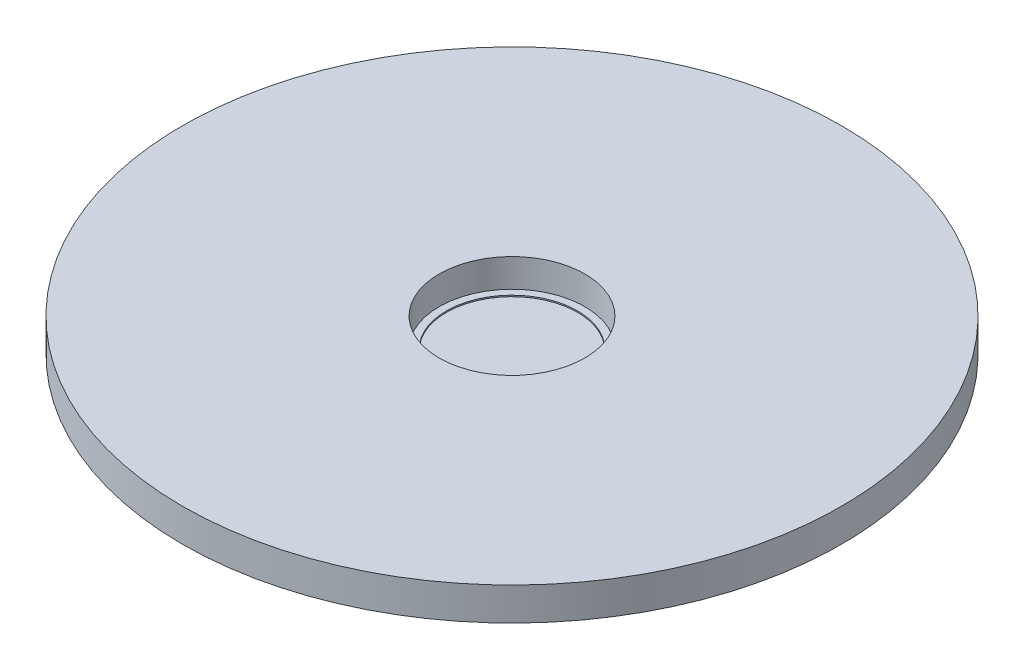
SolidWorks part; units mm, degrees
ref_plane "Front Plane" through (0, 0, 0) normal (0, 0, 1) x (1, 0, 0)
ref_plane "Top Plane" through (0, 0, 0) normal (0, 1, 0) x (1, 0, 0)
ref_plane "Right Plane" through (0, 0, 0) normal (1, 0, 0) x (0, 0, -1)
sketch "Sketch1" plane through (0, 0, 0) normal (0, 1, 0) x (1, 0, 0)
  circle A0 centre (0, 0) radius 50
  dimension "D1" = 100
extrude "Boss-Extrude1" add sketch "Sketch1" along normal blind 5
sketch "Sketch4" plane through (0, 5, 0) normal (0, 1, 0) x (1, 0, 0)
  circle A0 centre (0, 0) radius 11.05
  dimension "D1" = 22.1
extrude "Cut-Extrude2" cut sketch "Sketch4" against normal blind 4.5
sketch "Sketch5" plane through (0, 0.5, 0) normal (0, 1, 0) x (1, 0, 0)
  circle A0 centre (0, 0) radius 9.95
  circle A1 centre (0, 0) radius 11.05 construction
  circle A2 centre (0, 0) radius 11.05
  dimension "D1" = 1.1
extrude "Boss-Extrude4" add sketch "Sketch5" along normal blind 0.2
sketch "Sketch3" plane through (0, 5, 0) normal (0, 1, 0) x (1, 0, 0)
  line L0 (-5, -49.7494) -> (0, 0)
  line L1 (0, 0) -> (5, -49.7494)
  circle A1 centre (0, 0) radius 50 construction
  arc A2 (-5, -49.7494) -> (5, -49.7494) centre (0, 0) ccw
  arc A3 (-4.8, -47.7594) -> (4.8, -47.7594) centre (0, 0) ccw
  point P9 (0, -48)
  point P10 (0, -50)
  dimension "D1" = 2
  dimension "D2" = 10
extrude "Boss-Extrude2" [suppressed] add sketch "Sketch3" along normal blind 7.5
fillet "Fillet2" [suppressed] radius 4.75
fillet "Fillet3" [suppressed] radius 2
pattern_circular "CirPattern2" [suppressed] count 12 over 360 of bodies 110
